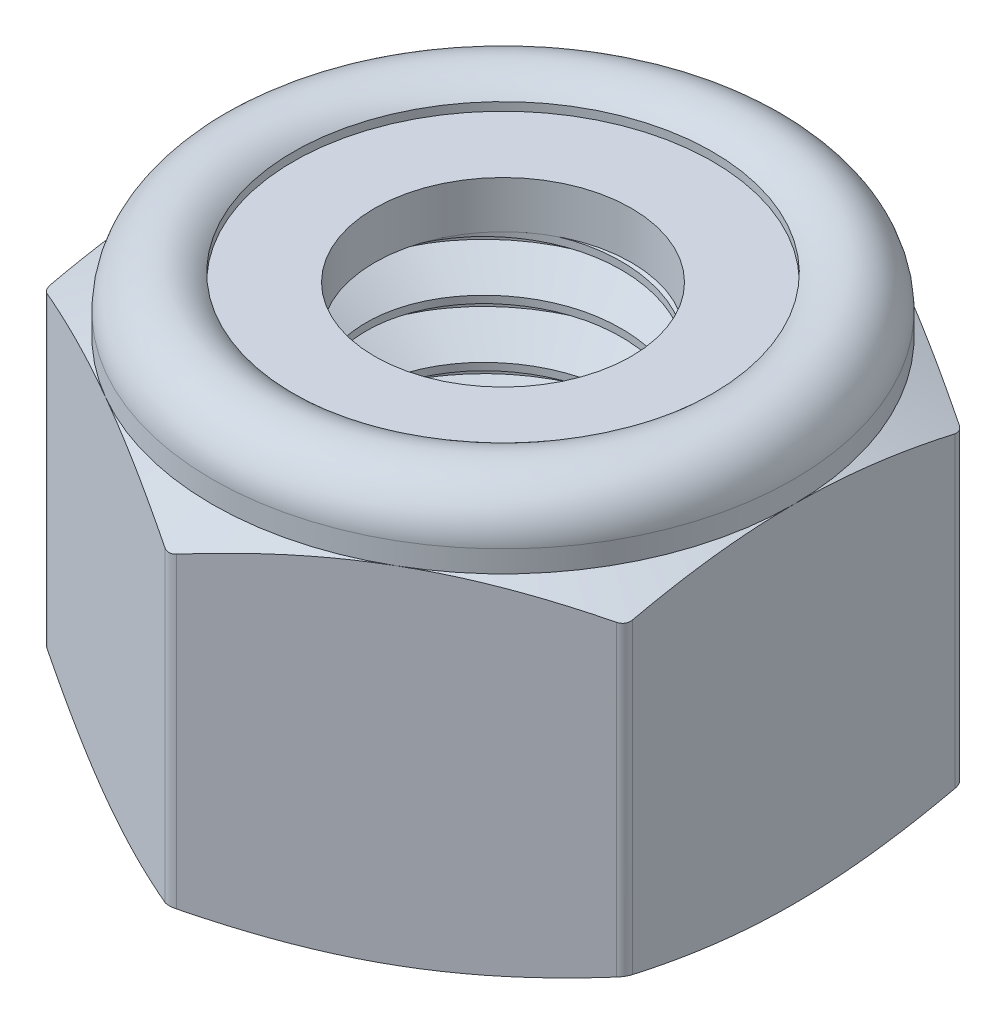
SolidWorks part; units mm, degrees
note: '?' marks a value the reader was unsure of.
material "Plain Carbon Steel"
ref_plane "Front Plane" through (0, 0, 0) normal (0, 0, 1) x (1, 0, 0)
ref_plane "Top Plane" through (0, 0, 0) normal (0, 1, 0) x (1, 0, 0)
ref_plane "Right Plane" through (0, 0, 0) normal (1, 0, 0) x (0, 0, -1)
sketch "Sketch1" plane through (0, 0, 0) normal (0, 0, 1) x (1, 0, 0)
  line L0 (0, -2.5) -> (0, 2.5) construction
  line L1 (3.5, 0) -> (-3.5, 0) construction
  line L2 (2, -2.5) -> (-2, -2.5) construction
  line L3 (2, -2.5) -> (2, -1.8) construction
  point P4 (0, 0)
  point P8 (0, 0)
  point P11 (0, -2.5)
  dimension "Height" = 5
  dimension "Width" = 7
  dimension "Thread Size" = 4
  dimension "Thread Pitch" = 0.7
sketch "Sketch2" plane through (0, 0, 0) normal (0, 1, 0) x (1, 0, 0)
  line L0 (-2, 0.3063) -> (-2, -0.3063) construction
  line L1 (0, 4.0415) -> (-3.5, 2.0207)
  line L2 (-3.5, 2.0207) -> (-3.5, -2.0207)
  line L3 (-3.5, -2.0207) -> (0, -4.0415)
  line L4 (0, -4.0415) -> (3.5, -2.0207)
  line L5 (3.5, -2.0207) -> (3.5, 2.0207)
  line L6 (3.5, 2.0207) -> (0, 4.0415)
  line L7 (-2, -0.3063) -> (-1.5453, -0.0438) construction
  line L8 (-1.5453, -0.0438) -> (-1.5453, 0.0437) construction
  line L9 (-1.5453, 0.0437) -> (-2, 0.3063) construction
  line L10 (-1.5453, 0) -> (-2, 0) construction
  line L11 (-1.7727, 0.175) -> (-1.7727, -0.175) construction
  line L12 (2, 0) -> (-2, 0) construction
  line L13 (3.5, 0) -> (-3.5, 0) construction
  circle A0 centre (0, 0) radius 3.5 construction
  circle A1 centre (0, 0) radius 1.5453
  point P19 (0, -1.5453)
  dimension "D1" = 0.0875
  dimension "D2" = 0.35
  dimension "D3" = 60
extrude "Boss-Extrude1" add sketch "Sketch2" along normal up to vertex (2.5 mm away) and the other way up to vertex (2.5 mm away) up to point (0, 2.5, 0) other way up to point (0, -2.5, 0)
fillet "Fillet1" radius 0.14 6 edges at (-3.5, 0, -2.0207) (0, 0, -4.0415) (-3.5, 0, 2.0207) (3.5, 0, -2.0207) (3.5, 0, 2.0207) (0, 0, 4.0415)
sketch "Sketch3" plane through (0, 0, 0) normal (1, 0, 0) x (0, 0, -1)
  line L0 (4.0415, 1.6667) -> (4.0415, 3.5)
  line L2 (3.5, -2.5) -> (4.0415, -2.2475)
  line L3 (2.0611, -2.5) -> (4.001, -2.5) construction
  line L4 (4.0415, 2.5) -> (4.0415, -2.5) construction
  line L5 (4.0415, -2.2475) -> (4.0415, -2.5)
  line L6 (4.0415, -2.5) -> (3.5, -2.5)
  line L7 (3.5, 1.6667) -> (4.0415, 1.4142)
  line L8 (4.0415, 1.4142) -> (4.0415, 1.6667)
  line L11 (3.5, 1.6667) -> (3.5, 1.9275)
  line L12 (2.0611, 2.5) -> (4.001, 2.5) construction
  line L13 (1.5453, 1.6667) -> (2.5227, 1.6667)
  line L14 (2.5227, 1.6667) -> (2.5227, 2.3323)
  line L15 (2.5227, 1.6667) -> (3.5, 1.6667) construction
  line L16 (2.5227, 2.3323) -> (2.9275, 1.9275) construction
  line L17 (2.9275, 1.9275) -> (2.9275, 2.5) construction
  line L18 (1.5453, 1.6667) -> (1.5453, 3.5)
  line L19 (1.5453, 3.5) -> (4.0415, 3.5)
  line L21 (1.5453, -2.5) -> (1.5453, -2.1)
  line L22 (-1.9399, -2.5) -> (1.9399, -2.5) construction
  line L24 (1.9453, -2.5) -> (1.5453, -2.5)
  line L25 (1.5453, -2.1) -> (1.9453, -2.5)
  arc A0 (3.5, 1.9275) -> (2.5227, 2.3323) centre (2.9275, 1.9275) ccw
  point P0 (3.5, 1.6667)
  point P1 (3.5, 0)
  point P14 (1.5453, 0)
  dimension "D1" = 4.1667
  dimension "D2" = 25
  dimension "D3" = 45
  dimension "D4" = 1
  dimension "D5" = 0.4
revolve "Cut-Revolve2" cut sketch "Sketch3" angle 360 about L0
sketch "Sketch4" plane through (0, 0, 0) normal (1, 0, 0) x (0, 0, -1)
  line L0 (-2.5227, 2.3323) -> (-2.5227, 1.6667) construction
  line L1 (-1.5453, 1.6667) -> (-2.5227, 1.6667)
  line L2 (-1.5453, 1.6667) -> (-1.5453, 2.2323)
  line L3 (-1.5453, 2.2323) -> (-2.5227, 2.2323)
  line L4 (-2.5227, 1.6667) -> (-2.5227, 2.2323)
  line L5 (2.5227, 2.3323) -> (-2.5227, 2.3323) construction
  line L6 (1.5453, 1.6667) -> (-1.5453, 1.6667) construction
  dimension "D1" = 0.1
revolve "Revolve1" add sketch "Sketch4" angle 360 about L0
sketch "Sketch5" plane through (0, 0, 0) normal (0, 1, 0) x (1, 0, 0)
  circle A0 centre (0, 0) radius 1.5453 construction
  point P0 (0, -1.5453)
sketch "Sketch6" plane through (0, 0, 0) normal (0, 0, 1) x (1, 0, 0)
  line L0 (2, 1.6667) -> (2, -2.5)
  line L2 (0, -2.5) -> (3.5, -2.5) construction
  line L3 (2, -2.5) -> (0, -2.5)
  line L4 (0, -2.5) -> (0, 1.6667)
  line L5 (0, -2.5) -> (0, 2.5) construction
  line L6 (0, 1.6667) -> (2, 1.6667)
  line L7 (3.5, 1.6667) -> (1.75, 1.6667) construction
revolve "Revolve2" add sketch "Sketch6" angle 360 about L4
sketch "Sketch7" plane through (0, -2.5, 0) normal (0, -1, 0) x (1, 0, 0)
  circle A2 centre (0, 0) radius 2
  circle A3 centre (0, 0) radius 2
  dimension "D1" = 0
curve "Helix/Spiral1" pitch 0.7 height 5 turns 7.1429
sketch "Sketch8" plane through (0, 0, 0) normal (0, 0, 1) x (1, 0, 0)
  line L0 (2.0758, -2.4563) -> (1.4696, -2.8063) construction
  line L1 (1.4696, -2.8063) -> (2.0758, -3.1563) construction
  line L2 (2.0758, -3.1563) -> (2.0758, -2.4563) construction
  line L3 (1.5453, -2.7625) -> (1.5453, -2.85)
  line L4 (2, -2.5) -> (2, -3.1125) construction
  line L5 (2, -2.8063) -> (2.0758, -2.8063) construction
  line L6 (1.4696, -2.8063) -> (1.5453, -2.8063) construction
  line L7 (2.0379, -2.8063) -> (2.0379, -3.1344) construction
  line L8 (1.5453, -2.7625) -> (2.0758, -2.4563)
  line L9 (2.0758, -2.4563) -> (2.0379, -3.1344)
  line L10 (1.5453, -2.85) -> (2.0379, -3.1344)
  dimension "D1" = 0.7
  dimension "D2" = 0.0875
sweep "Cut-Sweep1" cut profiles "Sketch8" path "Helix/Spiral1" align with end faces yes
sketch "Sketch9" plane through (0, 0, 0) normal (0, 0, 1) x (1, 0, 0)
  line L0 (0, -0.5) -> (0, -2.5)
  line L1 (0, -0.5) -> (0, -0.1)
  line L2 (0, -2.5) -> (2, -2.5)
  line L3 (2, -2.5) -> (2.4, -2.5)
  line L4 (2.4, -2.5) -> (0, -0.1)
  dimension "D1" = 0.4
revolve "Revolve3" add sketch "Sketch9" angle 360 about L0
sketch "Sketch10" plane through (0, -2.5, 0) normal (0, -1, 0) x (1, 0, 0)
  circle A0 centre (0, 0) radius 1.9453 construction
  circle A1 centre (0, 0) radius 1.9453
extrude "Boss-Extrude2" add sketch "Sketch10" against normal up to surface (4.1667 mm away) up to face at (2.5227, 1.6667, 0)
combine bodies "Combine1" operation type subtract main body 110 bodies to subtract 109
ref_axis "Axis1" through (0, 2.75, 0) along (0, -1, 0)?
equation "\"D1@Sketch3\"=\"Height@sketch1\"*(5/6)"
equation "\"D5@Sketch3\"=\"Thread Size@Sketch1\"*.1"
equation "\"D4@Helix/Spiral1\"=\"Thread Pitch@sketch1\""
equation "\"D3@Helix/Spiral1\"=\"Height@sketch1\""
equation "\"D1@Sketch8\"=\"Thread Pitch@sketch1\""
equation "\"D2@Sketch8\"=\"Thread Pitch@sketch1\"/8"
equation "\"D1@Sketch9\"=\"Thread Size@Sketch1\" * .1"
equation "\"D1@Sketch2\"=\"Thread Pitch@sketch1\"/8"
equation "\"D2@Sketch2\"=\"Thread Pitch@sketch1\"/2"
equation "\"D1@Sketch4\" = \"Height@Sketch1\" * .02"
equation "\"D1@Fillet1\"=\"Width@sketch1\"*.02"
